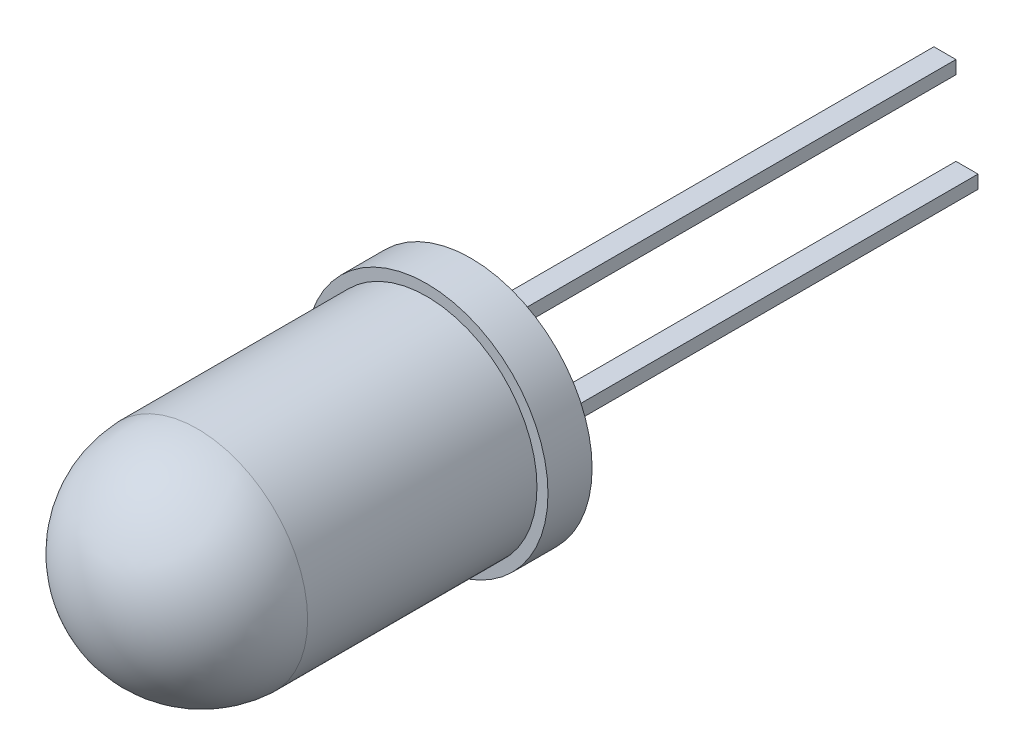
SolidWorks part; units mm, degrees
ref_plane "Front Plane" through (0, 0, 0) normal (0, 0, 1) x (1, 0, 0)
ref_plane "Top Plane" through (0, 0, 0) normal (0, 1, 0) x (1, 0, 0)
ref_plane "Right Plane" through (0, 0, 0) normal (1, 0, 0) x (0, 0, -1)
sketch "Sketch1" plane through (0, 0, 0) normal (0, 0, 1) x (1, 0, 0)
  circle A0 centre (0, 0) radius 2.5
  dimension "D1" = 5
extrude "Boss-Extrude1" add sketch "Sketch1" along normal mid plane 5.2
sketch "Sketch2" plane through (0, 0, 0) normal (0, 0, 1) x (1, 0, 0)
  circle A0 centre (0, 0) radius 2.75
  dimension "D1" = 5.5
extrude "Boss-Extrude2" add sketch "Sketch2" against normal blind 1 from surface starting at face at (2.5, 0, -2.6)
dome "Dome1" faces to dome 1 distance 2.4 reverse direction no elliptical dome no face at (2.5, 0, 2.6) parameters "D1"=2.4
sketch "Sketch3" plane through (0, 0, 0) normal (0, 0, 1) x (1, 0, 0)
  line L0 (1, 0) -> (0, 0) construction
  line L1 (1.5, 0.15) -> (1, 0.15)
  line L2 (1.5, 0.15) -> (1.5, -0.15)
  line L3 (1.5, -0.15) -> (1, -0.15)
  line L4 (1, 0.15) -> (1, -0.15)
  line L5 (-1, 0.15) -> (-1.5, 0.15)
  line L6 (-1, 0.15) -> (-1, -0.15)
  line L7 (-1, -0.15) -> (-1.5, -0.15)
  line L8 (-1.5, 0.15) -> (-1.5, -0.15)
  line L9 (0, 0) -> (-1, 0) construction
  point P8 (1, 0)
  point P9 (-1, 0)
  dimension "D1" = 0.5
  dimension "D2" = 0.3
  dimension "D3" = 2
extrude "Boss-Extrude3" add sketch "Sketch3" against normal blind 12 from surface starting at face at (2.75, 0, -3.6)
sketch "Sketch4" plane through (0, 0, 0) normal (0, 0, 1) x (1, 0, 0)
  line L1 (1, -0.15) -> (1.5, -0.15)
  line L2 (1, -0.15) -> (1, 0.15)
  line L3 (1, 0.15) -> (1.5, 0.15)
  line L4 (1.5, -0.15) -> (1.5, 0.15)
extrude "Cut-Extrude1" cut sketch "Sketch4" along normal blind 2 from surface starting at face at (1.25, 0, -15.6)
